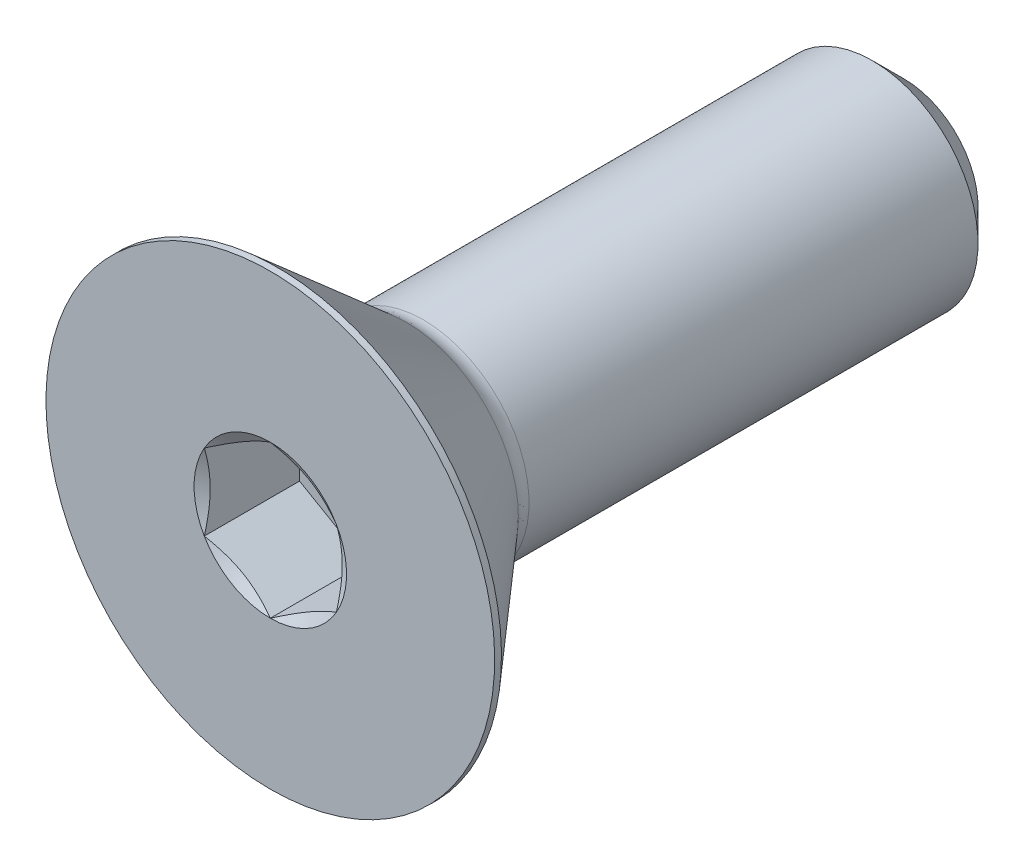
SolidWorks part; units mm, degrees
ref_plane "Front" through (0, 0, 0) normal (0, 0, 1) x (1, 0, 0)
ref_plane "Top" through (0, 0, 0) normal (0, 1, 0) x (1, 0, 0)
ref_plane "Right" through (0, 0, 0) normal (1, 0, 0) x (0, 0, -1)
sketch "Sketch1" plane through (0, 0, 0) normal (1, 0, 0) x (0, 0, -1)
  line L0 (0, 6.7437) -> (0.2045, 6.7437) construction
  line L1 (0.2045, 6.7437) -> (4.0894, 3.3666) construction
  line L2 (0, 3.175) -> (19.05, 3.175)
  line L3 (19.05, 3.175) -> (19.05, 0)
  line L4 (19.05, 0) -> (0, 0)
  line L5 (0, 0) -> (0, 6.7437) construction
  line L6 (0, 6.7437) -> (0, -6.7437) construction
  line L7 (19.05, 3.175) -> (19.05, -3.175) construction
  line L8 (0, -6.7437) -> (0.2045, -6.7437) construction
  line L9 (0.2045, -6.7437) -> (4.0894, -3.3666) construction
  line L11 (0, 3.175) -> (0, 0)
  line L12 (4.6018, 3.175) -> (4.6018, 0) construction
  line L13 (-6.35, 0) -> (-6.35, 3.175) construction
  arc A1 (4.0894, 3.3666) -> (4.6018, 3.175) centre (4.6018, 3.956) ccw construction
  dimension "D1" = 0.2045
  dimension "Min Thread" = 25.4
revolve "Revolve1" add sketch "Sketch1" angle 360 mid plane about L4
sketch "Sketch3" plane through (0, 0, -19.05) normal (0, 0, -1) x (-1, 0, 0)
  circle A0 centre (0, 0) radius 3.175
curve "Helix/Spiral1" pitch 1.27 height 19.05 turns 15
sketch "Sketch2" plane through (0, 0, 0) normal (1, 0, 0) x (0, 0, -1)
  line L0 (19.05, 3.175) -> (20.1612, 3.175)
  line L1 (20.1612, 3.175) -> (19.685, 2.3501)
  line L2 (19.685, 2.3501) -> (19.5263, 2.3501)
  line L3 (19.5263, 2.3501) -> (19.05, 3.175)
  line L4 (19.2881, 2.7626) -> (19.9231, 2.7626) construction
  dimension "D1" = 60
  dimension "D2" = 0.1588
  dimension "D3" = 0.635
ref_plane "Plane2" through (0, 0, 6.35) normal (0, 0, 1) x (1, 0, 0)
chamfer "Chamfer1" distance 0.9525 angle 45 1 edges at (0, 3.175, -19.05)
sweep "Cut-Sweep1" [suppressed] cut profiles "Sketch2" path "Helix/Spiral1"
sketch "Sketch7" plane through (0, 0, 0) normal (1, 0, 0) x (0, 0, -1)
  line L0 (0, 6.7437) -> (0.2045, 6.7437) construction
  line L1 (0.2045, 6.7437) -> (4.0894, 3.3666) construction
  line L2 (0, 6.7437) -> (0.2045, 6.7437)
  line L3 (0.2045, 6.7437) -> (4.0894, 3.3666)
  line L4 (4.6018, 3.175) -> (4.6018, 0) construction
  line L5 (4.6018, 3.175) -> (4.6018, 0)
  line L7 (0, 0) -> (0, 6.7437) construction
  line L8 (0, 0) -> (0, 6.7437)
  line L9 (0, 0) -> (4.6018, 0)
  line L10 (5.7417, 0) -> (-5.7417, 0) construction
  arc A0 (4.0894, 3.3666) -> (4.6018, 3.175) centre (4.6018, 3.956) ccw construction
  arc A1 (4.0894, 3.3666) -> (4.6018, 3.175) centre (4.6018, 3.956) ccw
revolve "Revolve2" add sketch "Sketch7" angle 360 mid plane about L9
ref_plane "Plane1" through (0, 0, -4.6018) normal (0, 0, 1) x (1, 0, 0)
sketch "Sketch8" plane through (0, 0, -4.6018) normal (0, 0, 1) x (1, 0, 0)
  circle A0 centre (0, 0) radius 3.175
extrude "Boss-Extrude1" add sketch "Sketch8" against normal through all draft 46
sketch "Sketch5" plane through (0, 0, 0) normal (0, 0, 1) x (1, 0, 0)
  line L0 (0, 0) -> (-2.2914, 0) construction
  line L1 (0, 0) -> (-2.7496, 1.5875) construction
  line L2 (0, 0) -> (-2.7496, -1.5875) construction
  line L6 (0, 2.2914) -> (0, 1.8898) construction
  line L7 (0, 1.8898) -> (0, 1.4883) construction
  line L9 (0, 2.2914) -> (-1.9844, 1.1457)
  line L10 (-1.9844, 1.1457) -> (-1.9844, -1.1457)
  line L11 (-1.9844, -1.1457) -> (0, -2.2914)
  line L12 (0, -2.2914) -> (1.9844, -1.1457)
  line L13 (1.9844, -1.1457) -> (1.9844, 1.1457)
  line L14 (1.9844, 1.1457) -> (0, 2.2914)
  circle A0 centre (0, 0) radius 2.2914 construction
  circle A1 centre (0, 0) radius 1.8898 construction
  circle A2 centre (0, 0) radius 1.4883 construction
  circle A3 centre (0, 0) radius 1.9844 construction
  dimension "D3" = 2.9766
  dimension "D4" = 30
  dimension "D5" = 30
  dimension "Hex" = 3.9688
extrude "Cut-Extrude2" cut sketch "Sketch5" against normal blind 2.8626
sketch "Sketch6" plane through (0, 0, 0) normal (0, 0, 1) x (1, 0, 0)
  circle A0 centre (0, 0) radius 2.2914
extrude "Cut-Extrude3" cut sketch "Sketch6" against normal blind 2.8626 draft 60
sketch "Sketch9" [suppressed] plane through (0, 0, -3.6076) normal (0, 0, 1) x (1, 0, 0)
  circle A1 centre (0, 0) radius 2.413
  circle A2 centre (0, 0) radius 2.413
  point P0 (0, 2.413)
  dimension "D1" = 0
extrude "Boss-Extrude2" [suppressed] add sketch "Sketch9" against normal up to surface (15.4424 mm away)
sketch "Sketch10" plane through (0, 0, 0) normal (1, 0, 0) x (0, 0, -1)
  line L0 (19.05, 3.175) -> (19.05, -3.175) construction
  point P0 (17.145, -3.175)
  dimension "D1" = 1.905
equation "\"D3@Helix/Spiral1\" = \"Lg@Sketch1\""
equation "\"D2@Sketch2\" = \"D4@Helix/Spiral1\" * .125"
equation "\"D3@Sketch2\" = \"D4@Helix/Spiral1\" * .5"
equation "\"D1@Chamfer1\" = \"D4@Helix/Spiral1\" * .75"
equation "\"D1@Cut-Extrude2\" = \"Head Ht@Sketch1\" * .7"
equation "\"D1@Sketch1\" = \"Head Ht@Sketch1\" * .05"
equation "\"D1@Sketch10\" = \"D4@Helix/Spiral1\" * 1.5"
equation "\"D1@Cut-Extrude3\" = \"D1@Cut-Extrude2\""
equation "\"D3@Sketch5\" = \"Hex@Sketch5\" * .75"
